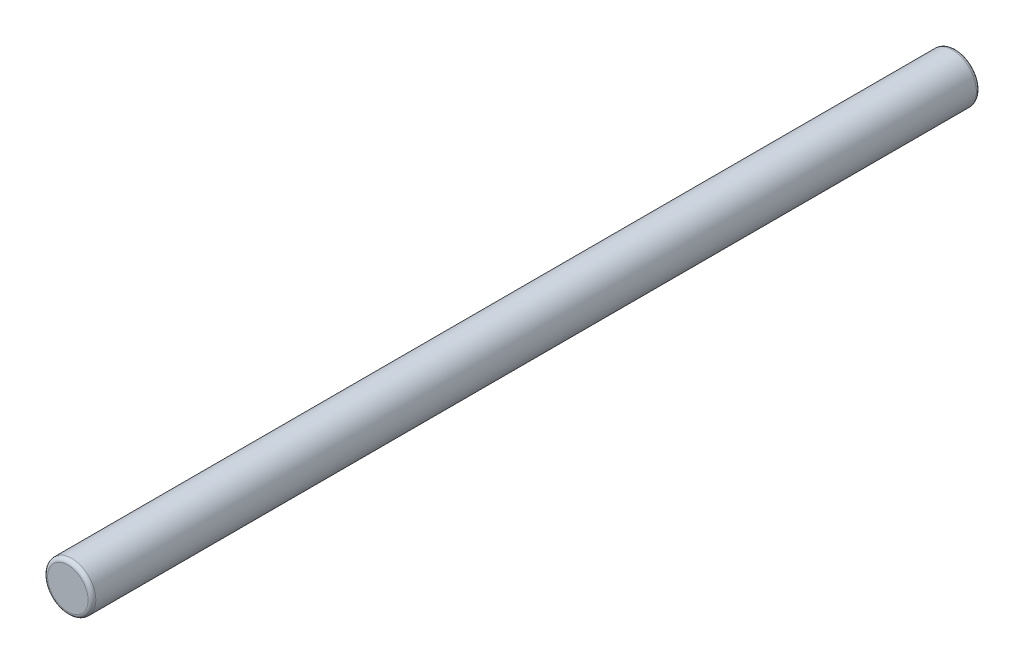
SolidWorks part; units mm, degrees
material "1.0037 (S235JR)"
ref_plane "Ön Düzlem" through (0, 0, 0) normal (0, 0, 1) x (1, 0, 0)
ref_plane "Üst Düzlem" through (0, 0, 0) normal (0, 1, 0) x (1, 0, 0)
ref_plane "Sağ Düzlem" through (0, 0, 0) normal (1, 0, 0) x (0, 0, -1)
sketch "Çizim1" plane through (0, 0, 0) normal (0, 0, 1) x (1, 0, 0)
  circle A0 centre (0, 0) radius 12.5
  dimension "D1" = 25
extrude "Yükseklik-Ekstrüzyon1" add sketch "Çizim1" along normal blind 230 and the other way blind 230
sketch "Çizim2" plane through (0, 0, 0) normal (0, 1, 0) x (1, 0, 0)
  circle A0 centre (0, 100) radius 4.25
  circle A1 centre (0, -100) radius 4.25
  dimension "D1" = 8.5
  dimension "D2" = 8.5
  dimension "D3" = 100
  dimension "D4" = 100
extrude "Kes-Ekstrüzyon1" cut sketch "Çizim2" against normal blind 50
cosmetic thread "Kozmetik Diş Açma1"
cosmetic thread "Kozmetik Diş Açma2"
fillet "Radyus1" radius 2 2 edges at (12.5, 0, 230) (12.5, 0, -230)
